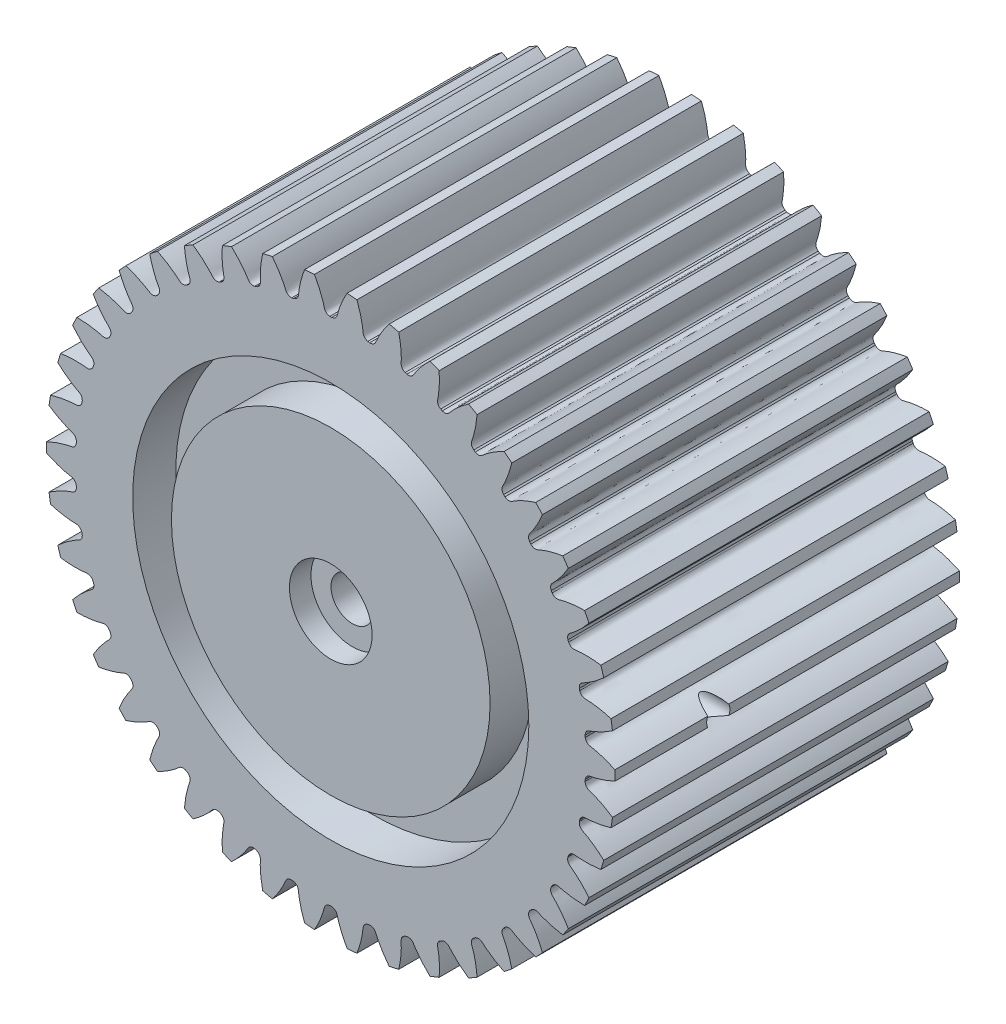
SolidWorks part; units mm, degrees
ref_plane "前视基准面" through (0, 0, 0) normal (0, 0, 1) x (1, 0, 0)
ref_plane "上视基准面" through (0, 0, 0) normal (0, 1, 0) x (1, 0, 0)
ref_plane "右视基准面" through (0, 0, 0) normal (1, 0, 0) x (0, 0, -1)
sketch "草图1" plane through (0, 0, 0) normal (0, 0, 1) x (1, 0, 0)
  circle A0 centre (0, 0) radius 33
extrude "凸台-拉伸1" add sketch "草图1" along normal blind 40
ref_axis "基准轴1" through (0, 0, -1.5) along (0, 0, 1)
sketch "草图2" plane through (0, 0, 0) normal (0, 0, 1) x (1, 0, 0)
  line L0 (0, 0) -> (0, 33) construction
  circle A0 centre (0, 0) radius 33 construction
  arc A1 (0.1074, 29.6248) -> (-0.1074, 29.6248) centre (0, 0) ccw
  arc A2 (5.56, 37.4744) -> (-5.56, 37.4744) centre (0, 0) ccw
  spline S0 degree 3 poles (0.1074, 29.6248) (0.6754, 29.7068) (0.733, 30.1211) (0.8585, 30.5673) (0.9042, 30.7198) (0.9566, 30.8825) (1.0162, 31.0554) (1.0832, 31.2382) (1.1582, 31.4306) (1.2415, 31.6324) (1.3336, 31.8433) (1.4348, 32.0632) (1.5456, 32.2916) (1.6663, 32.5283) (1.7973, 32.773) (1.9389, 33.0253) (2.0916, 33.285) (2.2556, 33.5517) (2.4314, 33.8249) (2.6191, 34.1045) (2.8192, 34.3899) (3.032, 34.6808) (3.2577, 34.9768) (3.4967, 35.2776) (3.7492, 35.5826) (4.0154, 35.8915) (4.2957, 36.2038) (4.5903, 36.519) (5.0079, 36.9484) (5.335, 37.265) (5.56, 37.4744) knots 0 0 0 0 0.112032 0.12724 0.143671 0.161325 0.180201 0.2003 0.221621 0.244165 0.267931 0.29292 0.319132 0.346566 0.375223 0.405102 0.436204 0.468529 0.502076 0.536845 0.572837 0.610052 0.648489 0.688149 0.729032 0.771136 0.814464 0.859014 0.904787 1 1 1 1
  spline S1 degree 3 poles (-0.1074, 29.6248) (-0.6754, 29.7068) (-0.733, 30.1211) (-0.8585, 30.5673) (-0.9042, 30.7198) (-0.9566, 30.8825) (-1.0162, 31.0554) (-1.0832, 31.2382) (-1.1582, 31.4306) (-1.2415, 31.6324) (-1.3336, 31.8433) (-1.4348, 32.0632) (-1.5456, 32.2916) (-1.6663, 32.5283) (-1.7973, 32.773) (-1.9389, 33.0253) (-2.0916, 33.285) (-2.2556, 33.5517) (-2.4314, 33.8249) (-2.6191, 34.1045) (-2.8192, 34.3899) (-3.032, 34.6808) (-3.2577, 34.9768) (-3.4967, 35.2776) (-3.7492, 35.5826) (-4.0154, 35.8915) (-4.2957, 36.2038) (-4.5903, 36.519) (-5.0079, 36.9484) (-5.335, 37.265) (-5.56, 37.4744) knots 0 0 0 0 0.112032 0.12724 0.143671 0.161325 0.180201 0.2003 0.221621 0.244165 0.267931 0.29292 0.319132 0.346566 0.375223 0.405102 0.436204 0.468529 0.502076 0.536845 0.572837 0.610052 0.648489 0.688149 0.729032 0.771136 0.814464 0.859014 0.904787 1 1 1 1
extrude "切除-拉伸1" cut sketch "草图2" along normal through all
pattern_circular "阵列(圆周)1" count 42 every 8.571 about axis through (0, 0, -1.5) along (0, 0, 1) of "切除-拉伸1"
sketch "草图3" plane through (0, 0, 0) normal (0, 0, 1) x (1, 0, 0)
  circle A0 centre (0, 0) radius 31.5 construction
  dimension "Dn" = 63
sketch "草图4" plane through (0, 0, 40) normal (0, 0, 1) x (1, 0, 0)
  line L1 (-1.475, -15.71) -> (1.475, -15.71)
  line L2 (-1.475, -15.71) -> (-1.475, 15.71)
  line L3 (-1.475, 15.71) -> (1.475, 15.71)
  line L4 (1.475, -15.71) -> (1.475, 15.71)
  line L5 (-1.475, -15.71) -> (1.475, 15.71) construction
  line L6 (-1.475, 15.71) -> (1.475, -15.71) construction
  circle A0 centre (0, 0) radius 2.5
  point P0 (0, 0)
  dimension "D2" = 5
  dimension "D1" = 2.95
sketch "草图5" plane through (0, 0, 40) normal (0, 0, 1) x (1, 0, 0)
  circle A0 centre (0, 0) radius 4.8
  dimension "D1" = 9.6
extrude "切除-拉伸2" cut sketch "草图5" against normal blind 2.5
sketch "草图6" plane through (0, 0, 37.5) normal (0, 0, 1) x (1, 0, 0)
  circle A0 centre (0, 0) radius 2.475
  dimension "D1" = 4.95
extrude "切除-拉伸3" cut sketch "草图6" against normal blind 4.6
sketch "草图7" plane through (0, 0, 32.9) normal (0, 0, 1) x (1, 0, 0)
  line L1 (-1.475, -15.71) -> (1.475, -15.71)
  line L2 (-1.475, -15.71) -> (-1.475, 15.71)
  line L3 (-1.475, 15.71) -> (1.475, 15.71)
  line L4 (1.475, -15.71) -> (1.475, 15.71)
  line L5 (-1.475, -15.71) -> (1.475, 15.71) construction
  line L6 (-1.475, 15.71) -> (1.475, -15.71) construction
  circle A2 centre (0, 0) radius 2.475
  circle A3 centre (0, 0) radius 2.475
  circle M6 centre (0, 0) radius 2.475
  dimension "D2" = 2.95
  dimension "D1" = 0
extrude "切除-拉伸4" cut sketch "草图7" against normal blind 11 contours L4 L2 M6 region at (0, 0, 32.9)
sketch "草图8" plane through (0, 0, 0) normal (1, 0, 0) x (0, -1, 0)
  line L0 (0, 0) -> (0, -28) construction
  circle A0 centre (0, -28) radius 1.35
  dimension "D2" = 2.7
  dimension "D1" = 28
extrude "切除-拉伸6" cut sketch "草图8" against normal through all both and the other way through all
sketch "草图9" plane through (0, 0, 40) normal (0, 0, 1) x (1, 0, 0)
  circle A0 centre (0, 0) radius 20.5
  circle A1 centre (0, 0) radius 23
  circle A2 centre (0, 0) radius 18.5
  dimension "D1" = 41
  dimension "D2" = 46
  dimension "D3" = 37
extrude "切除-拉伸7" cut sketch "草图9" against normal blind 5 contours A0 A2 | A1 A0 region at (-19.9202, 0, 40) region at (-22.3495, 0, 40)
